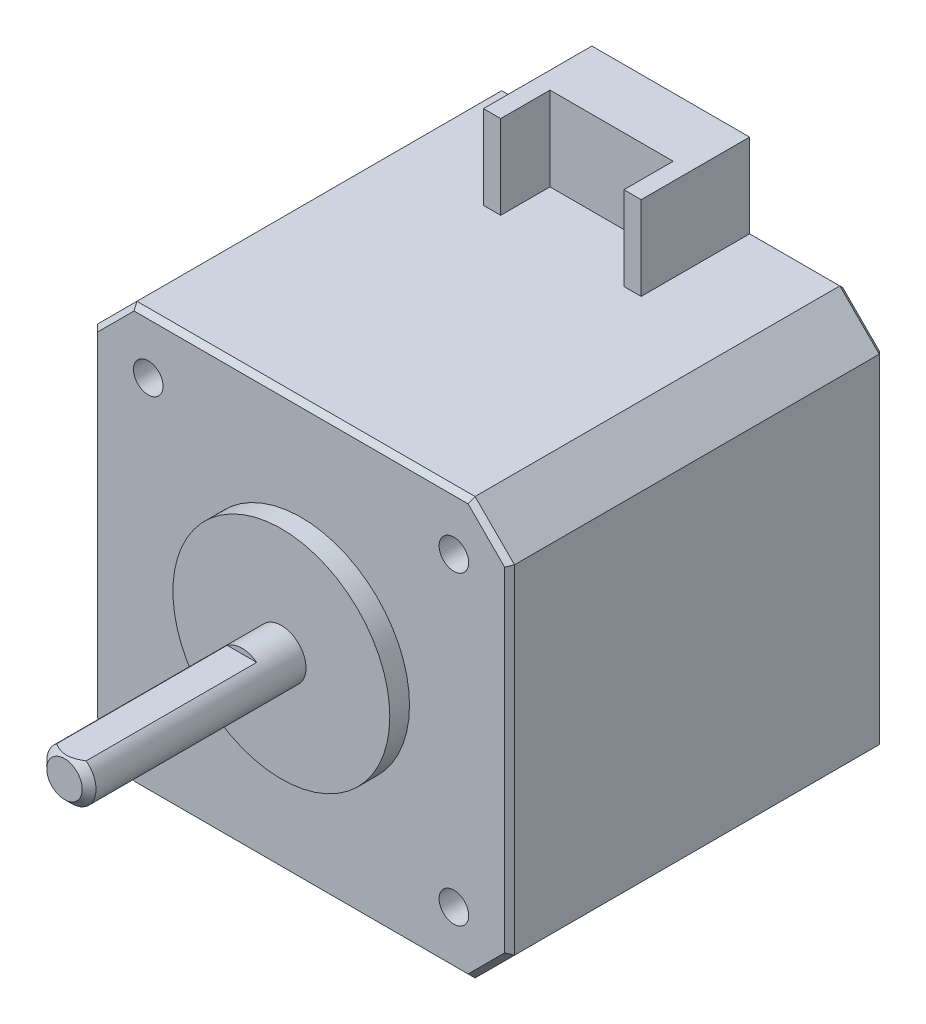
SolidWorks part; units mm, degrees
ref_plane "Front Plane" through (0, 0, 0) normal (0, 0, 1) x (1, 0, 0)
ref_plane "Top Plane" through (0, 0, 0) normal (0, 1, 0) x (1, 0, 0)
ref_plane "Right Plane" through (0, 0, 0) normal (1, 0, 0) x (0, 0, -1)
sketch "Sketch1" plane through (0, 0, 0) normal (0, 0, 1) x (1, 0, 0)
  line L1 (-21.15, -21.15) -> (21.15, -21.15)
  line L2 (-21.15, -21.15) -> (-21.15, 21.15)
  line L3 (-21.15, 21.15) -> (21.15, 21.15)
  line L4 (21.15, -21.15) -> (21.15, 21.15)
  line L5 (-21.15, -21.15) -> (21.15, 21.15) construction
  line L6 (-21.15, 21.15) -> (21.15, -21.15) construction
  circle A0 centre (-15.5, 15.5) radius 1.5
  circle A1 centre (15.5, 15.5) radius 1.5
  circle A2 centre (15.5, -15.5) radius 1.5
  circle A3 centre (-15.5, -15.5) radius 1.5
  point P0 (0, 0)
  dimension "D2" = 3
  dimension "D1" = 42.3
  dimension "D3" = 31
extrude "Boss-Extrude1" add sketch "Sketch1" along normal blind 38 contours L1 L4 L3 L2 A3 A2 A1 A0 | A3 | A2 | A1 | A0 region at (0, 0, 0) region at (-15.5, 15.5, 0) region at (15.5, 15.5, 0) region at (15.5, -15.5, 0) region at (-15.5, -15.5, 0)
sketch "Sketch2" plane through (0, 0, 38) normal (0, 0, 1) x (1, 0, 0)
  circle A0 centre (0, 0) radius 11
  circle A1 centre (0, 0) radius 2.5
  dimension "D1" = 22
  dimension "D2" = 5
extrude "Boss-Extrude2" add sketch "Sketch2" along normal blind 2 contours A0 A1 region at (-10.6889, 0, 38)
extrude "Boss-Extrude3" add sketch "Sketch2<3>" along normal blind 24 contours A1 region at (0, 0, 38)
sketch "Sketch2<3>" plane through (0, 0, 38) normal (0, 0, 1) x (1, 0, 0) same geometry as "Sketch2"
sketch "Sketch3" plane through (0, 0, 38) normal (0, 0, 1) x (1, 0, 0)
  line L4 (-21.15, -21.15) -> (21.15, -21.15)
  line L5 (21.15, -21.15) -> (21.15, 21.15)
  line L6 (21.15, 21.15) -> (-21.15, 21.15)
  line L7 (-21.15, 21.15) -> (-21.15, -21.15)
  line L8 (-21.15, -21.15) -> (21.15, -21.15)
  line L9 (21.15, -21.15) -> (21.15, 21.15)
  line L10 (21.15, 21.15) -> (-21.15, 21.15)
  line L11 (-21.15, 21.15) -> (-21.15, -21.15)
  circle A0 centre (-15.5, -15.5) radius 1.5 construction
  circle A1 centre (-15.5, -15.5) radius 1.5
  circle A2 centre (15.5, -15.5) radius 1.5 construction
  circle A3 centre (15.5, 15.5) radius 1.5 construction
  circle A4 centre (-15.5, 15.5) radius 1.5 construction
  circle A5 centre (15.5, -15.5) radius 1.5
  circle A6 centre (15.5, 15.5) radius 1.5
  circle A7 centre (-15.5, 15.5) radius 1.5
  dimension "D1" = 0
extrude "Cut-Extrude1" cut sketch "Sketch3" against normal blind 5 contours A1 | A5 | A6 | A7 region at (-15.5, -15.5, 38) region at (15.5, -15.5, 38) region at (15.5, 15.5, 38) region at (-15.5, 15.5, 38)
chamfer "Chamfer1" distance 4 angle 45 4 edges at (-21.15, 21.15, 19) (21.15, 21.15, 19) (21.15, -21.15, 19) (-21.15, -21.15, 19)
chamfer "Chamfer2" distance 0.7 angle 45 1 edges at (2.5, 0, 62)
sketch "Sketch4" plane through (0, 0, 0) normal (0, 0, -1) x (-1, 0, 0)
  circle A0 centre (0, 0) radius 8
  circle A1 centre (0, 0) radius 2.5
  dimension "D1" = 16
  dimension "D2" = 5
extrude "Cut-Extrude2" cut sketch "Sketch4" against normal blind 0.5 contours A0 A1 region at (7.7737, 0, 0)
chamfer "Chamfer3" distance 0.3 angle 45 1 edges at (-2.5, 0, 0)
chamfer "Chamfer4" distance 0.5 angle 45 16 edges at (0, 21.15, 38) (-19.15, 19.15, 38) (-21.15, 0, 38) (21.15, 0, 38) (19.15, -19.15, 38) (0, -21.15, 38) (-19.15, -19.15, 38) (19.15, 19.15, 0) (21.15, 0, 0) (19.15, -19.15, 0) (0, -21.15, 0) (-19.15, -19.15, 0) (-21.15, 0, 0) (-19.15, 19.15, 0) (0, 21.15, 0) (19.15, 19.15, 38)
sketch "Sketch5" plane through (0, 0, 0) normal (0, 0, -1) x (-1, 0, 0)
  line L0 (-15.5, 15.5) -> (15.5, 15.5) construction
  line L1 (15.5, 15.5) -> (15.5, -15.5) construction
  line L3 (-14, 16.366) -> (-15.5, 17.2321)
  line L4 (-15.5, 17.2321) -> (-17, 16.366)
  line L5 (-17, 16.366) -> (-17, 14.634)
  line L6 (-17, 14.634) -> (-15.5, 13.7679)
  line L7 (-15.5, 13.7679) -> (-14, 14.634)
  line L8 (-14, 14.634) -> (-14, 16.366)
  line L9 (17, 16.366) -> (15.5, 17.2321)
  line L10 (15.5, 17.2321) -> (14, 16.366)
  line L11 (14, 16.366) -> (14, 14.634)
  line L12 (14, 14.634) -> (15.5, 13.7679)
  line L13 (15.5, 13.7679) -> (17, 14.634)
  line L14 (17, 14.634) -> (17, 16.366)
  line L15 (17, -16.366) -> (17, -14.634)
  line L16 (17, -14.634) -> (15.5, -13.7679)
  line L17 (15.5, -13.7679) -> (14, -14.634)
  line L18 (14, -14.634) -> (14, -16.366)
  line L19 (14, -16.366) -> (15.5, -17.2321)
  line L20 (15.5, -17.2321) -> (17, -16.366)
  line L21 (-14, -14.634) -> (-15.5, -13.7679)
  line L22 (-15.5, -13.7679) -> (-17, -14.634)
  line L23 (-17, -14.634) -> (-17, -16.366)
  line L24 (-17, -16.366) -> (-15.5, -17.2321)
  line L25 (-15.5, -17.2321) -> (-14, -16.366)
  line L26 (-14, -16.366) -> (-14, -14.634)
  circle A0 centre (-15.5, 15.5) radius 3
  circle A1 centre (15.5, 15.5) radius 3
  circle A2 centre (15.5, -15.5) radius 3
  circle A3 centre (-15.5, -15.5) radius 3
  circle A4 centre (-15.5, 15.5) radius 1.5 construction
  circle A5 centre (15.5, 15.5) radius 1.5 construction
  circle A6 centre (15.5, -15.5) radius 1.5 construction
  circle A7 centre (-15.5, -15.5) radius 1.5 construction
  point P8 (15.5, 0)
  point P9 (0, 15.5)
  dimension "D1" = 6
  dimension "D4" = 3
  dimension "D2" = 31
  dimension "D3" = 31
extrude "Cut-Extrude3" cut sketch "Sketch5" against normal blind 0.5 contours A0 L8 L7 L6 L5 L4 L3 | A1 L14 L13 L12 L11 L10 L9 | A2 L20 L19 L18 L17 L16 L15 | A3 L26 L25 L24 L23 L22 L21 region at (18.4151, 15.5, 0) region at (-12.5849, 15.5, 0) region at (-12.5849, -15.5, 0) region at (18.4151, -15.5, 0)
extrude "Cut-Extrude4" cut sketch "Sketch5<3>" against normal blind 2 contours L7 L8 L3 L4 L5 L6 | L13 L14 L9 L10 L11 L12 | L19 L20 L15 L16 L17 L18 | L25 L26 L21 L22 L23 L24 region at (15.5, 15.5, 0) region at (-15.5, 15.5, 0) region at (-15.5, -15.5, 0) region at (15.5, -15.5, 0)
sketch "Sketch5<3>" plane through (0, 0, 0) normal (0, 0, -1) x (-1, 0, 0) same geometry as "Sketch5"
chamfer "Chamfer5" distance 0.3 angle 45 4 edges at (12.5, -15.5, 0) (12.5, 15.5, 0) (-18.5, 15.5, 0) (-18.5, -15.5, 0)
sketch "Sketch6" plane through (0, 0, 62) normal (0, 0, 1) x (1, 0, 0)
  line L0 (-1.5, 2) -> (1.5, 2)
  circle A0 centre (0, 0) radius 2.5 construction
  circle A1 centre (0, 0) radius 2.5
  arc A3 (-1.5, 2) -> (1.5, 2) centre (0, 0) cw
  dimension "D1" = 4.5
extrude "Cut-Extrude5" cut sketch "Sketch6" against normal blind 18 contours L0 A1 region at (0, 2.2018, 62)
sketch "Sketch7" plane through (0, 21.15, 0) normal (0, 1, 0) x (1, 0, 0)
  line L0 (17.15, -0.5) -> (-17.15, -0.5) construction
  line L1 (-8, -0.5) -> (8, -0.5)
  line L2 (-8, -0.5) -> (-8, -11.5)
  line L3 (-8, -11.5) -> (8, -11.5)
  line L4 (8, -0.5) -> (8, -11.5)
  line L6 (-6.25, -11.5) -> (6.25, -11.5)
  line L7 (-6.25, -11.5) -> (-6.25, -6.5)
  line L8 (-6.25, -6.5) -> (6.25, -6.5)
  line L9 (6.25, -11.5) -> (6.25, -6.5)
  point P6 (0, -0.5)
  point P12 (0, -6.5)
  line M6 (17.15, -0.5) -> (-17.15, -0.5)
  dimension "D1" = 16
  dimension "D2" = 11
  dimension "D3" = 12.5
  dimension "D4" = 5
extrude "Boss-Extrude5" add sketch "Sketch7" along normal blind 8.5 contours L9 L3 L4 L2 L7 L8 M6 region at (0, 21.15, 4.348)
